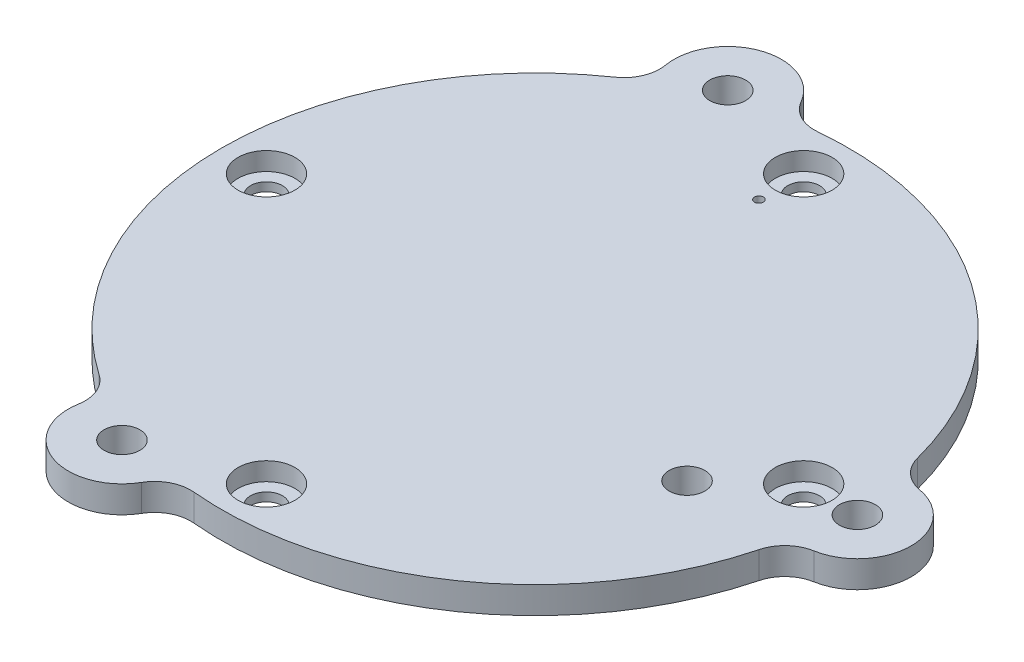
SolidWorks part; units mm, degrees
material "1060 Alloy"
ref_plane "Front Plane" through (0, 0, 0) normal (0, 0, 1) x (1, 0, 0)
ref_plane "Top Plane" through (0, 0, 0) normal (0, 1, 0) x (1, 0, 0)
ref_plane "Right Plane" through (0, 0, 0) normal (1, 0, 0) x (0, 0, -1)
sketch "Sketch1" plane through (0, 0, 0) normal (0, 1, 0) x (1, 0, 0)
  circle A0 centre (0, 0) radius 17.5
  dimension "D1" = 35
extrude "Boss-Extrude1" add sketch "Sketch1" along normal blind 1.5
sketch "Sketch6" plane through (0, 1.5, 0) normal (0, 1, 0) x (1, 0, 0)
  line L0 (0, 0) -> (19.3341, -5.1806) construction
  line L1 (0, 0) -> (17.9741, 0) construction
  circle A0 centre (0, 12.5) radius 0.25
  circle A1 centre (11.5911, -3.1058) radius 1
  dimension "D1" = 12.5
  dimension "D3" = 0.5
  dimension "D4" = 2
  dimension "D2" = 0
  dimension "D5" = 12
  dimension "D6" = 15
extrude "Cut-Extrude1" cut sketch "Sketch6" against normal through all both and the other way through all
hole_wizard "CBORE for #0 Socket Head Cap Screw1" positions "Sketch7" profile "Sketch8" counterbore size "#0" standard "ANSI Inch" end condition through all
sketch "Sketch7" plane through (0, 1.5, 0) normal (0, 1, 0) x (1, 0, 0)
  point P0 (0, 15)
  point P2 (-15, 0)
  point P4 (0, -15)
  point P6 (15, 0)
  dimension "D1" = 15
  dimension "D2" = 15
  dimension "D3" = 15
  dimension "D4" = 15
sketch "Sketch8" plane through (0, 1.5, -15) normal (1, 0, 0) x (0, 0, 1)
  line L0 (0, 0) -> (0, 1.5)
  line L1 (0, 1.5) -> (0.889, 1.5)
  line L3 (0.889, 1.5) -> (0.889, 1.016)
  line L4 (0.889, 1.016) -> (1.5875, 1.016)
  line L5 (1.5875, 1.016) -> (1.5875, 0)
  line L7 (1.5875, 0) -> (0, 0)
  line L11 (0, -6.35) -> (0, 107.95) construction
  dimension "Thru Hole Dia." = 1.778
  dimension "Thru Hole Depth" = 1.5
  dimension "C'Bore Dia." = 3.175
  dimension "C'Bore Depth" = 1.016
sketch "Sketch9" plane through (0, 0, 0) normal (0, -1, 0) x (1, 0, 0)
  line L0 (-6.1564, 16.9145) -> (0, 0) construction
  line L1 (0, 0) -> (-6.1564, -16.9145) construction
  line L2 (-6.1564, -16.9145) -> (0, 0) construction
  line L3 (0, 0) -> (18, 0) construction
  line L4 (-3.2616, 17.702) -> (2.8948, 0.7876)
  line L5 (-8.8801, 15.6571) -> (-2.7238, -1.2574)
  line L6 (17.75, 2.9896) -> (-0.25, 2.9896)
  line L7 (17.75, -2.9896) -> (-0.25, -2.9896)
  line L8 (-8.8801, -15.6571) -> (-2.7238, 1.2574)
  line L9 (-3.2616, -17.702) -> (2.8948, -0.7876)
  circle A0 centre (0, 0) radius 18
  circle A1 centre (-6.1564, 16.9145) radius 1
  circle A2 centre (-6.1564, -16.9145) radius 1
  circle A3 centre (18, 0) radius 1
  circle A4 centre (18, 0) radius 3
  circle A5 centre (-6.1564, -16.9145) radius 3
  circle A6 centre (-6.1564, 16.9145) radius 3
  circle A7 centre (0, 0) radius 3
  circle M10 centre (0, 0) radius 17.5
  dimension "D1" = 2
  dimension "D2" = 2
  dimension "D3" = 2
  dimension "D4" = 36
  dimension "D7" = 6
  dimension "D8" = 6
  dimension "D9" = 6
  dimension "D10" = 6
  dimension "D5" = 140
  dimension "D6" = 110
extrude "Boss-Extrude2" add sketch "Sketch9" against normal up to surface (1.5 mm away) contours A0 A4 A3 | A4 L6 M10 | A4 L7 M10 | A0 A5 A2 | A0 A5 A2 M10 | A5 L9 M10 | A5 L8 M10 | A0 A6 A1 | A6 A0 A1 M10 | A6 L4 M10 | A6 L5 M10 | A5 A0 A2 M10 | A0 A5 A2 M10 | A4 A0 A3 M10 | A0 A4 A3 M10 | A0 A6 A1 M10 | A6 A0 A1 M10 region at (-4.194, 0, 17.2363) region at (-6.6097, 0, 18.1601) region at (-3.1659, 0, 17.3639) region at (17.3995, 0, 2.9638) region at (19.3255, 0, 0) region at (17.6312, 0, 1.9541) region at (-8.7361, 0, 15.3365) region at (-7.8665, 0, 15.8996) region at (-7.8665, 0, -15.8996) region at (-6.6097, 0, -18.1601) region at (-8.7361, 0, -15.3365) region at (17.6312, 0, -1.9541) region at (17.3995, 0, -2.9638) region at (-3.1659, 0, -17.3639) region at (-4.194, 0, -17.2363) up to face at (0, 1.5, -13.4125)
fillet "Fillet1" radius 2 6 edges at (17.2428, 0.75, 2.9896) (-3.0881, 0.75, 17.2254) (-8.7066, 0.75, 15.1804) (-8.7066, 0.75, -15.1804) (-3.0881, 0.75, -17.2254) (17.2428, 0.75, -2.9896)
sketch "Sketch10" plane through (0, 1.5, 0) normal (0, 1, 0) x (1, 0, 0)
  circle A0 centre (-6.1564, 16.9145) radius 1
  circle A1 centre (18, 0) radius 1
  circle A2 centre (-6.1564, -16.9145) radius 1
extrude "Cut-Extrude2" cut sketch "Sketch10" against normal blind 10
